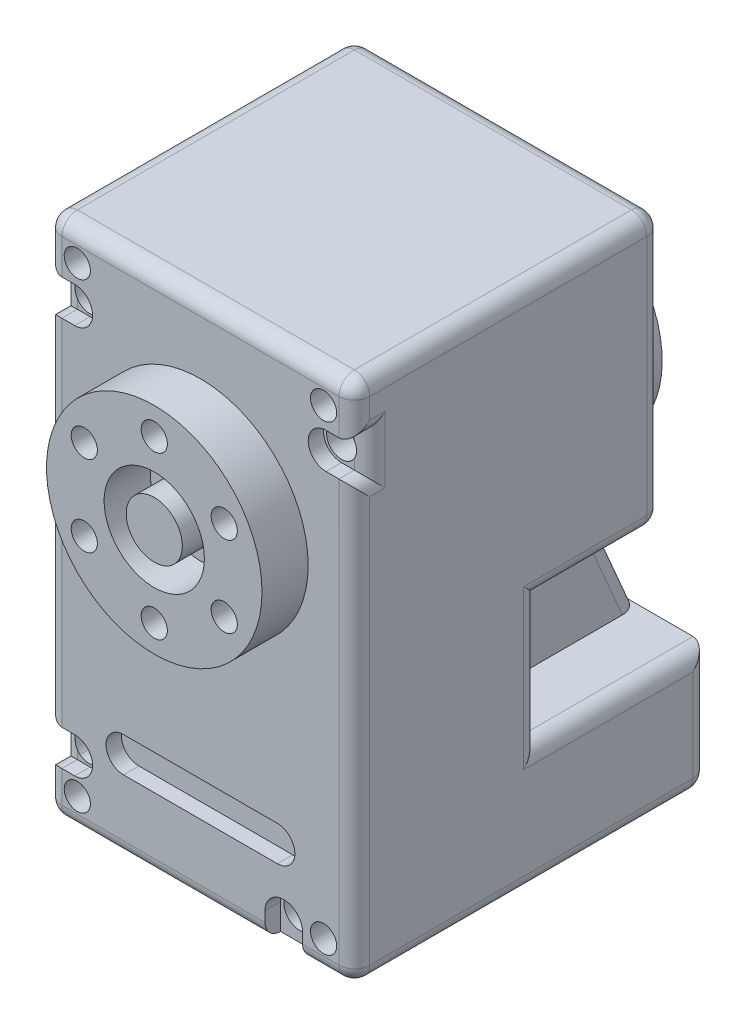
SolidWorks part; units mm, degrees
ref_plane "前视基准面" through (0, 0, 0) normal (0, 0, 1) x (1, 0, 0)
ref_plane "上视基准面" through (0, 0, 0) normal (0, 1, 0) x (1, 0, 0)
ref_plane "右视基准面" through (0, 0, 0) normal (1, 0, 0) x (0, 0, -1)
other "Configuration Table"
sketch "草图1" plane through (0, 0, 0) normal (0, 0, 1) x (1, 0, 0)
  line L0 (0, 0) -> (20, 0)
  line L1 (20, 0) -> (20, 34)
  line L2 (20, 34) -> (0, 34)
  line L3 (0, 34) -> (0, 0)
  line L4 (10, 0) -> (10, 34) construction
  line L5 (0, 17) -> (20, 17) construction
  circle A0 centre (2, 32) radius 0.85
  circle A1 centre (18, 32) radius 0.85
  circle A2 centre (18, 2) radius 0.85
  circle A3 centre (2, 2) radius 0.85
  circle A4 centre (10, 22.5) radius 7
  circle A5 centre (10, 27.75) radius 0.8504
  circle A6 centre (14.5466, 25.125) radius 0.8504
  circle A7 centre (14.5466, 19.875) radius 0.8504
  circle A8 centre (10, 17.25) radius 0.8504
  circle A9 centre (5.4534, 19.875) radius 0.8504
  circle A10 centre (5.4534, 25.125) radius 0.8504
  circle A11 centre (10, 22.5) radius 5.25
  circle A12 centre (10, 22.5) radius 3.2575
  circle A13 centre (10, 22.5) radius 1.8232
  point P34 (10, 22.5)
  dimension "D3" = 1.7
  dimension "D7" = 6
  dimension "D8" = 14
  dimension "D9" = 10.5
  dimension "D1" = 20
  dimension "D2" = 34
  dimension "D4" = 16
  dimension "D5" = 30
  dimension "D6" = 9.5
extrude "凸台-拉伸4" add sketch "草图1" along normal blind 3 contours A4 A11 A6 A7 A8 A9 A10 A5 | A6 A11 A5 A10 A9 A8 A7 A12 | A13 region at (3.198, 22.5, 0) region at (10, 26.7521, 0) region at (10, 22.5, 0)
sketch "草图3" plane through (0, 0, 3) normal (0, 0, 1) x (1, 0, 0)
extrude "凸台-拉伸5" add sketch "草图1<9>" against normal blind 20 contours A11 A7 | A7 A11 | A11 A5 | A11 A10 | A10 A11 | A11 A9 | A9 A11 | A11 A8 | A8 A11 | A6 A11 A5 A10 A9 A8 A7 A12 | A12 A13 | A13 | A1 | A0 | A2 | A3 | L2 L3 L0 L1 A4 A1 A0 A2 A3 | A4 A11 A6 A7 A8 A9 A10 A5 | A5 A11 | A6 region at (10, 15.3623, 0) region at (2, 32, 0) region at (18, 32, 0) region at (18, 2, 0) region at (2, 2, 0) region at (3.198, 22.5, 0) region at (10, 28.0982, 0) region at (10, 27.377, 0) region at (10, 26.7521, 0) region at (5.1518, 25.2991, 0) region at (5.7764, 24.9385, 0) region at (5.1518, 19.7009, 0) region at (5.7764, 20.0615, 0) region at (14.2236, 20.0615, 0) region at (14.8482, 19.7009, 0) region at (10, 16.9018, 0) region at (10, 17.623, 0) region at (6.8346, 22.5, 0) region at (10, 22.5, 0)
sketch "草图1<9>" plane through (0, 0, 0) normal (0, 0, 1) x (1, 0, 0) same geometry as "草图1"
sketch "草图4" plane through (0, 0, 0) normal (0, 0, 1) x (1, 0, 0)
sketch "草图6" plane through (0, 0, 0) normal (0, 0, 1) x (1, 0, 0)
sketch "草图7" plane through (0, 0, 0) normal (0, 0, 1) x (1, 0, 0)
  line L0 (10, 0) -> (10, 35.4001) construction
  line L1 (20, 0) -> (20, 34) construction
  line L2 (0, 17) -> (20, 17) construction
  line L3 (0, 0) -> (20, 0) construction
  circle A0 centre (2, 32) radius 0.85
  circle A3 centre (18, 32) radius 0.85
  circle A4 centre (18, 2) radius 0.85
  circle A5 centre (2, 2) radius 0.85
  dimension "D3" = 10
  dimension "D1" = 16
  dimension "D2" = 30
  dimension "D4" = 17
extrude "切除-拉伸1" cut sketch "草图7" against normal blind 1.5 contours A0 | A5 | A3 | A4
sketch "草图8" plane through (0, 0, 0) normal (-1, 0, 0) x (0, 0, 1)
  line L0 (-20, 0) -> (-23, 0)
  line L1 (-23, 0) -> (-23, 8)
  line L2 (-23, 8) -> (-20, 16)
  line L3 (-20, 34) -> (-20, 0) construction
  line L4 (-20, 16) -> (-20, 0)
  line L5 (-20, 34) -> (0, 34) construction
  line L6 (-20, 16) -> (-16, 16)
  line L7 (-16, 16) -> (-16, 8)
  line L8 (-16, 8) -> (-20, 8)
  line L9 (-23, 8) -> (-20, 8)
  dimension "D1" = 3
  dimension "D2" = 18
  dimension "D3" = 4
  dimension "D4" = 8
extrude "凸台-拉伸6" add sketch "草图8" against normal blind 20 contours L9 L1 L0 L4 region at (0, 4, -21.5)
sketch "草图9" plane through (0, 0, -20) normal (0, 0, -1) x (-1, 0, 0)
  line L0 (-10, 8) -> (-10, 13.8742) construction
  line L2 (0, 34) -> (0, 8) construction
  dimension "D1" = 10
sketch "草图11" plane through (0, 0, 0) normal (-1, 0, 0) x (0, 0, 1)
  line L0 (-23, 8) -> (-20, 15)
  line L1 (-20, -199992) -> (-20, 200013.8742) construction
  line L2 (-20, 15) -> (-20, 8)
  line L3 (-20, 8) -> (-23, 8)
  dimension "D1" = 7
extrude "凸台-拉伸7" add sketch "草图11" against normal blind 20
sketch "草图12" plane through (0, 0, 0) normal (-1, 0, 0) x (0, 0, 1)
  line L0 (-23, 8) -> (-20, 8)
  line L1 (-20, -199992) -> (-20, 200013.8742) construction
  line L2 (-20, 8) -> (-20, 15)
  line L3 (-20, 15) -> (-23, 8)
extrude "切除-拉伸2" cut sketch "草图12" against normal blind 4.5
sketch "草图13" plane through (20, 0, 0) normal (1, 0, 0) x (0, 0, -1)
  line L0 (23, 8) -> (20, 8)
  line L1 (20, -199992) -> (20, 200013.8742) construction
  line L2 (20, 8) -> (20, 15)
  line L3 (20, 15) -> (23, 8)
extrude "切除-拉伸3" cut sketch "草图13" against normal blind 4.5 contours L3 L0 L2
sketch "草图14" plane through (0, 0, -20) normal (0, 0, -1) x (-1, 0, 0)
  line L0 (-20, 0) -> (0, 0)
  line L1 (0, 0) -> (0, 34)
  line L2 (0, 34) -> (-20, 34)
  line L3 (-20, 34) -> (-20, 0)
  line L4 (-10, 0) -> (-10, 34) construction
  line L5 (-20, 17) -> (0, 17) construction
  circle A0 centre (-18, 32) radius 0.85
  circle A1 centre (-2, 32) radius 0.85
  circle A2 centre (-2, 2) radius 0.85
  circle A3 centre (-18, 2) radius 0.85
  circle A4 centre (-10, 22.5) radius 7
  circle A5 centre (-10, 27.75) radius 0.8504
  circle A11 centre (-10, 22.5) radius 5.25
  circle A12 centre (-10, 22.5) radius 3.2575
  circle A13 centre (-10, 22.5) radius 1.8232
  circle A14 centre (-5.4534, 25.125) radius 0.8504
  circle A15 centre (-5.4534, 19.875) radius 0.8504
  circle A16 centre (-10, 17.25) radius 0.8504
  circle A17 centre (-14.5466, 19.875) radius 0.8504
  circle A18 centre (-14.5466, 25.125) radius 0.8504
  point P32 (-10, 22.5)
  point P38 (-10, 22.5)
  dimension "D2" = 1.7
  dimension "D5" = 14
  dimension "D6" = 10.5
  dimension "D1" = 34
  dimension "D3" = 30
  dimension "D4" = 9.5
  dimension "D7" = 6
extrude "凸台-拉伸8" add sketch "草图14" along normal blind 3 contours A4 A11 A18 A5 A14 A15 A16 A17 | A11 A18 A17 A16 A15 A14 A5 A12 | A13 region at (16.802, 22.5, -20) region at (10, 26.7521, -20) region at (10, 22.5, -20)
sketch "草图15" plane through (0, 0, 0) normal (0, 0, 1) x (1, 0, 0)
  line L0 (0, 4.2275) -> (1.8335, 4.2275) construction
  line L4 (15.4187, -0.3137) -> (15.4187, 1.681) construction
  line L5 (14.1999, -0.3137) -> (14.1999, 1.681)
  line L6 (16.6374, -0.3137) -> (16.6374, 1.681)
  line L7 (0, 34) -> (0, 0) construction
  line L8 (0, 5.3867) -> (1.8335, 5.3867)
  line L9 (0, 3.0682) -> (1.8335, 3.0682)
  line L10 (-0.0011, 29.5642) -> (1.8324, 29.5642) construction
  line L11 (-0.0011, 30.7235) -> (1.8324, 30.7235)
  line L12 (-0.0011, 28.405) -> (1.8324, 28.405)
  line L13 (18.1621, 29.5159) -> (19.9956, 29.5159) construction
  line L14 (18.1621, 30.6752) -> (19.9956, 30.6752)
  line L15 (18.1621, 28.3567) -> (19.9956, 28.3567)
  line L16 (5, 5.8457) -> (15, 5.8457) construction
  line L17 (5, 6.9809) -> (15, 6.9809)
  line L18 (5, 4.7105) -> (15, 4.7105)
  line L19 (10, -199992) -> (10, 200013.8742) construction
  arc A2 (14.1999, -0.3137) -> (16.6374, -0.3137) centre (15.4187, -0.3137) ccw
  arc A3 (16.6374, 1.681) -> (14.1999, 1.681) centre (15.4187, 1.681) ccw
  arc A4 (0, 5.3867) -> (0, 3.0682) centre (0, 4.2275) ccw
  arc A5 (1.8335, 3.0682) -> (1.8335, 5.3867) centre (1.8335, 4.2275) ccw
  arc A6 (-0.0011, 30.7235) -> (-0.0011, 28.405) centre (-0.0011, 29.5642) ccw
  arc A7 (1.8324, 28.405) -> (1.8324, 30.7235) centre (1.8324, 29.5642) ccw
  arc A8 (18.1621, 30.6752) -> (18.1621, 28.3567) centre (18.1621, 29.5159) ccw
  arc A9 (19.9956, 28.3567) -> (19.9956, 30.6752) centre (19.9956, 29.5159) ccw
  arc A10 (5, 6.9809) -> (5, 4.7105) centre (5, 5.8457) ccw
  arc A11 (15, 4.7105) -> (15, 6.9809) centre (15, 5.8457) ccw
  point P4 (0.9167, 4.2275)
  point P11 (10, 5.8457)
  point P14 (15.4187, 0.6837)
  point P23 (0.9157, 29.5642)
  point P30 (19.0789, 29.5159)
  dimension "D1" = 5
  dimension "D2" = 5
extrude "切除-拉伸4" cut sketch "草图15" against normal blind 1 contours L11 A7 L12 A6 | L14 A9 L15 A8 | L18 A11 L17 A10 | L5 A3 L6 A2 | L9 A5 L8 A4
sketch "草图16" plane through (0, 0, -1) normal (0, 0, 1) x (1, 0, 0)
  circle A0 centre (15.4271, 1.685) radius 1
  circle A1 centre (1.8311, 4.1874) radius 0.9947
  circle A2 centre (1.8324, 29.5642) radius 1
  circle A3 centre (18.1621, 29.5159) radius 0.988
  dimension "D1" = 2
sketch "草图18" plane through (0, 0, -20) normal (0, 0, -1) x (-1, 0, 0)
  line L0 (0, 16.1746) -> (-4.6877, 16.1746)
  line L1 (0, 34) -> (0, 8) construction
  line L2 (-4.6877, 16.1746) -> (-4.6877, 8)
  line L3 (-15.5, 8) -> (-4.5, 8) construction
  line L4 (-4.6877, 8) -> (0, 8)
  line L5 (0, 16.1746) -> (0, 8)
sketch "草图19" plane through (0, 0, 0) normal (-1, 0, 0) x (0, 0, 1)
extrude "切除-拉伸5" cut sketch "草图18" against normal blind 8 and the other way through all contours L4 L5 L0 L2
sketch "草图20" plane through (0, 0, -20) normal (0, 0, -1) x (-1, 0, 0)
  line L0 (-15.5, 8) -> (-15.5, 16.2997)
  line L1 (-15.5, 16.2997) -> (-20, 16.2997)
  line L2 (-20, 8) -> (-20, 34) construction
  line L3 (-20, 16.2997) -> (-20, 8)
  line L4 (-20, 8) -> (-15.5, 8)
  line L5 (-4.6877, 16.1746) -> (-15.0917, 16.1746)
extrude "切除-拉伸6" cut sketch "草图20" against normal blind 8 and the other way through all contours L4 L0 L1 L3
sketch "草图28" plane through (4.6877, 0, 0) normal (-1, 0, 0) x (0, 0, 1)
  line L0 (-23, 8) -> (-12, 8)
  line L1 (-12, 8) -> (-12, 16.1746)
  line L2 (-12, 16.1746) -> (-20, 16.1746)
  line L3 (-20, 16.1746) -> (-20, 15)
  line L4 (-20, -199992) -> (-20, 200013.8742) construction
  line L5 (-23, 8) -> (-20, 15) construction
  line L6 (-20, 15) -> (-23, 8)
extrude "凸台-拉伸9" add sketch "草图28" along normal blind 0.19
sketch "草图29" plane through (0, 0, 0) normal (0, 0, 1) x (1, 0, 0)
  circle A0 centre (1.8324, 29.5642) radius 1
  circle A1 centre (18.1621, 29.5159) radius 0.9725
  circle A2 centre (15.4271, 1.685) radius 1
  circle A3 centre (1.8311, 4.1874) radius 1
  circle A4 centre (1.7631, 4.2422) radius 1
  point P7 (18.1621, 29.5159)
  point P11 (2.4483, 15.5)
  point P12 (1.8311, 4.1874)
  point P16 (15.4271, 1.685)
extrude "切除-拉伸7" cut sketch "草图29" against normal blind 3 contours A3 A4 | A2 | A0 | A1 region at (1.8324, 29.5642, 0) region at (18.1621, 29.5159, 0) region at (15.4271, 1.685, 0) region at (1.7971, 4.2148, 0)
fillet "圆角1" radius 1 33 edges at (0, 16.1746, -16) (0, 25.0873, -20) (0, 34, -10) (0, 32.3617, 0) (0, 30.7235, -0.5) (0, 29.5642, -1) (0, 28.405, -0.5) (0, 16.8958, 0) (0, 5.3867, -0.5) (0, 4.2275, -1) (0, 3.0682, -0.5) (0, 1.5341, 0) (0, 0, -11.5) (0, 4, -23) (0, 8, -17.5) (0, 12.0873, -12) (20, 4, -23) (20, 0, -11.5) (20, 14.1783, 0) (20, 32.3376, 0) (20, 34, -10) (20, 25.1498, -20) (20, 16.2997, -16) (20, 12.1498, -12) (20, 8, -17.5) (10, 34, 0) (18.3187, 0, 0) (7.1, 0, 0) (10, 0, -23) (10, 34, -20)
fillet "圆角3" radius 1 8 edges at (0.2929, 16.4675, -19.7071) (19.7071, 16.5925, -19.7071) (15.5, 11.5, -21.5) (4.4977, 15.5873, -20) (2.7488, 16.1746, -20) (4.4977, 11.5, -21.5) (15.5, 15.6498, -20) (17.25, 16.2997, -20)
